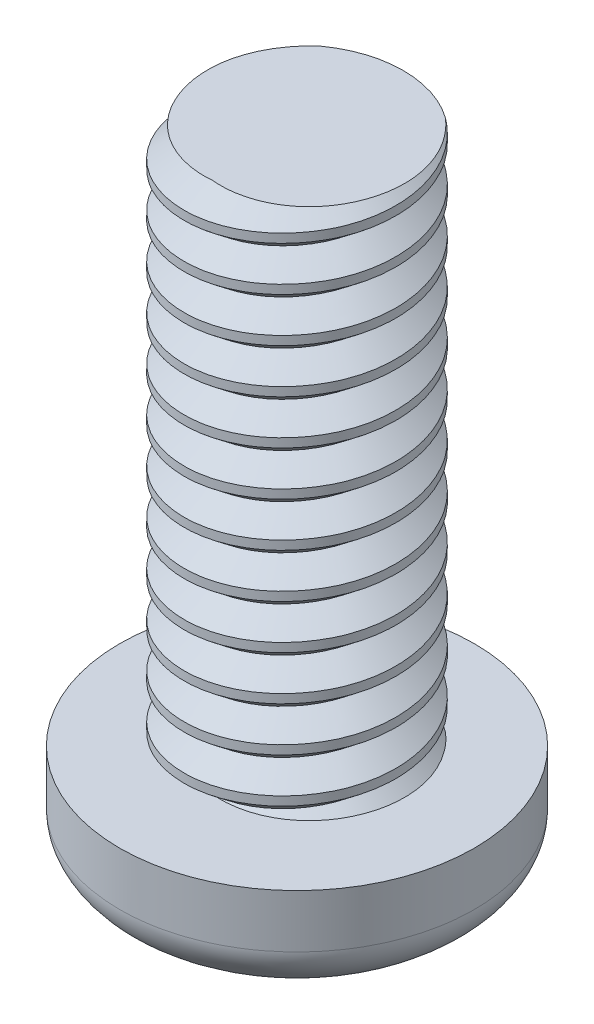
SolidWorks part; units mm, degrees
ref_plane "前视基准面" through (0, 0, 0) normal (0, 0, 1) x (1, 0, 0)
ref_plane "上视基准面" through (0, 0, 0) normal (0, 1, 0) x (1, 0, 0)
ref_plane "右视基准面" through (0, 0, 0) normal (1, 0, 0) x (0, 0, -1)
sketch "草图1" plane through (0, 0, 0) normal (0, 1, 0) x (1, 0, 0)
  circle A0 centre (0, 0) radius 1
  dimension "D1" = 2
extrude "凸台-拉伸1" add sketch "草图1" along normal blind 0.7
sketch "草图2" plane through (0, 0.7, 0) normal (0, 1, 0) x (1, 0, 0)
  circle A0 centre (0, 0) radius 0.6
  dimension "D1" = 1.2
extrude "凸台-拉伸2" add sketch "草图2" along normal blind 3
sketch "草图3" plane through (0, 0, 0) normal (0, -1, 0) x (-1, 0, 0)
  line L0 (0, 0.5) -> (0, 0) construction
  line L1 (-1, 0) -> (1.0313, 0) construction
  line L2 (0.5, 0) -> (0, 0) construction
  line L3 (0, -0.5) -> (0, 0) construction
  line L4 (-0.5, 0) -> (0, 0) construction
  line L5 (-0.15, 0.5) -> (-0.15, 0.15)
  line L6 (0.5, 0.15) -> (0.15, 0.15)
  line L7 (0.15, -0.5) -> (0.15, -0.15)
  line L8 (-0.5, -0.15) -> (-0.15, -0.15)
  line L9 (0.15, 0.5) -> (0.15, 0.15)
  line L10 (0.5, -0.15) -> (0.15, -0.15)
  line L11 (-0.15, -0.5) -> (-0.15, -0.15)
  line L12 (-0.5, 0.15) -> (-0.15, 0.15)
  line L13 (-0.15, -0.5) -> (-0.15, 0) construction
  line L14 (-0.5, -0.15) -> (0, -0.15) construction
  line L15 (0.5, -0.15) -> (0, -0.15) construction
  line L16 (0.15, -0.5) -> (0.15, 0) construction
  line L17 (0.15, 0.5) -> (0.15, 0) construction
  line L18 (0.5, 0.15) -> (0, 0.15) construction
  line L19 (-0.5, 0.15) -> (0, 0.15) construction
  line L20 (-0.15, 0.5) -> (-0.15, 0) construction
  circle A1 centre (0, 0) radius 1 construction
  arc A2 (-0.15, 0.5) -> (0.15, 0.5) centre (0, 0.5) cw
  arc A3 (-0.15, 0) -> (0.15, 0) centre (0, 0) ccw construction
  arc A4 (0.5, 0.15) -> (0.5, -0.15) centre (0.5, 0) cw
  arc A5 (0, 0.15) -> (0, -0.15) centre (0, 0) ccw construction
  arc A6 (0.15, -0.5) -> (-0.15, -0.5) centre (0, -0.5) cw
  arc A7 (0.15, 0) -> (-0.15, 0) centre (0, 0) ccw construction
  arc A8 (-0.5, -0.15) -> (-0.5, 0.15) centre (-0.5, 0) cw
  arc A9 (0, -0.15) -> (0, 0.15) centre (0, 0) ccw construction
  point P13 (0, 0)
  dimension "D1" = 0.5
  dimension "D3" = 0.15
  dimension "D4" = 0.15
  dimension "D2" = 4
extrude "切除-拉伸2" cut sketch "草图3" against normal blind 0.5
fillet "圆角2" radius 0.8 1 edges at (0, 0, 1) second distance 0.4 first distance on face at (0, 0, 0)
sketch "草图5" plane through (0, 3.7, 0) normal (0, 1, 0) x (1, 0, 0)
  circle A0 centre (0, 0) radius 0.6
  dimension "D1" = 1.2
curve "螺旋线/涡状线1" pitch 0.25 height 3 radius 0.6 centre (0, 3.7, 0) axis (0, -1, 0) start towards (0, 0, 1)
sketch "草图12" plane through (0, 0, 0) normal (1, 0, 0) x (0, 0, -1)
  line L0 (-0.6, 3.8) -> (-0.6, 3.6)
  line L1 (-0.6, 3.6) -> (-0.475, 3.7)
  line L2 (-0.475, 3.7) -> (-0.6, 3.8)
  point P0 (-0.6, 3.7)
  point P5 (-0.6, 3.7)
  point P6 (0, 0)
  point P7 (0, 0)
  dimension "D1" = 0.2
  dimension "D2" = 0.125
sweep "切除-扫描1" cut profiles "草图12" path "螺旋线/涡状线1" align with end faces yes
